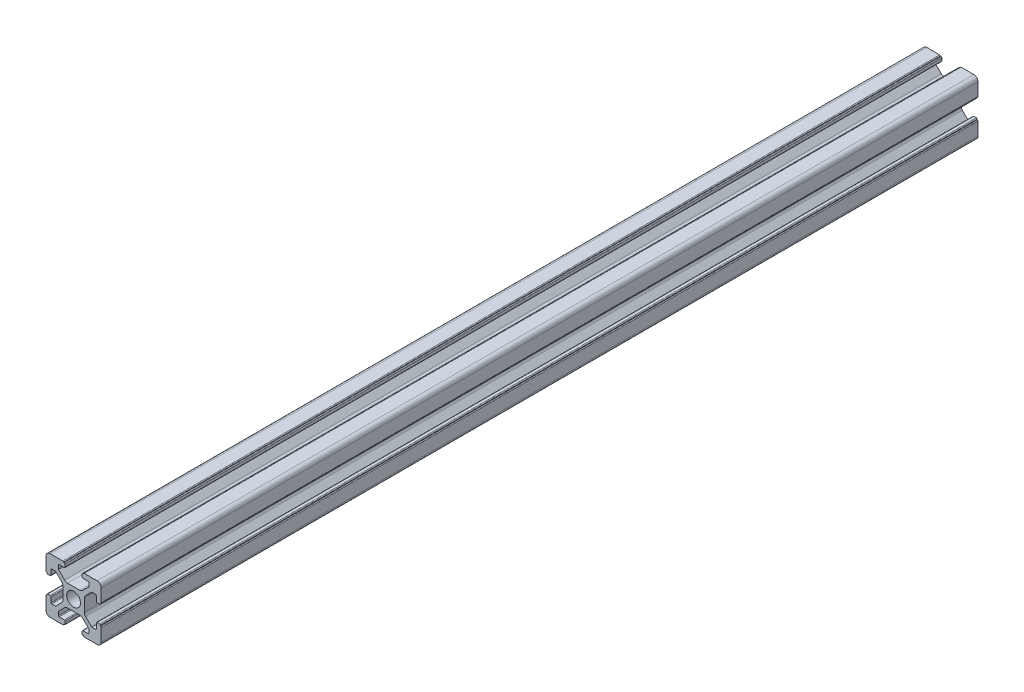
SolidWorks part; units mm, degrees
material "1060 Alloy"
ref_plane "Front Plane" through (0, 0, 0) normal (0, 0, 1) x (1, 0, 0)
ref_plane "Top Plane" through (0, 0, 0) normal (0, 1, 0) x (1, 0, 0)
ref_plane "Right Plane" through (0, 0, 0) normal (1, 0, 0) x (0, 0, -1)
sketch "Sketch1" plane through (0, 0, 0) normal (0, 0, 1) x (1, 0, 0)
  line L0 (3.8995, 3.9005) -> (10.4604, 10.4604) construction
  line L2 (-3.9002, 2.2177) -> (-3.9002, -2.2208)
  line L5 (-3.9005, 3.899) -> (3.9001, -3.8986) construction
  line L6 (-3.9, -3.901) -> (3.8995, 3.9005) construction
  line L7 (-0.0002, 10) -> (-0.0002, -9.9996) construction
  line L8 (-0.0002, -9.9996) -> (-0.0002, 10) construction
  line L9 (5.5006, 6.5619) -> (3.2793, 4.3405)
  line L14 (-10.0002, 9.9996) -> (9.9994, -10) construction
  line L15 (-9.9999, -10.0001) -> (9.9998, 10) construction
  line L16 (6.5613, 5.5012) -> (4.3401, 3.28)
  line L17 (-5.5002, 6.5603) -> (-3.279, 4.3391)
  line L18 (-6.5609, 5.4996) -> (-4.3395, 3.2783)
  line L19 (7.9206, 5.5012) -> (6.5613, 5.5012)
  line L20 (8.2006, 3.3812) -> (8.2006, 5.2212)
  line L21 (9.4206, 3.1012) -> (8.4806, 3.1012)
  line L22 (9.7006, 3.6012) -> (9.7006, 3.3812)
  line L23 (-8.5002, 9.9996) -> (-3.8802, 9.9996)
  line L24 (-3.6002, 9.7196) -> (-3.6002, 9.6996)
  line L25 (-3.6002, 9.6996) -> (-3.3802, 9.6996)
  line L26 (-3.1002, 9.4196) -> (-3.1002, 8.4796)
  line L27 (-3.3802, 8.1996) -> (-5.2202, 8.1996)
  line L28 (-5.5002, 7.9196) -> (-5.5002, 6.5603)
  line L29 (-7.9202, 5.4996) -> (-6.5609, 5.4996)
  line L30 (-8.2002, 3.3796) -> (-8.2002, 5.2196)
  line L31 (-9.4202, 3.0996) -> (-8.4802, 3.0996)
  line L32 (-9.7202, 3.5996) -> (-9.7002, 3.5996)
  line L33 (-9.7002, 3.5996) -> (-9.7002, 3.3796)
  line L34 (-10.0002, 8.4996) -> (-10.0002, 3.8796)
  line L35 (10.0006, 8.5012) -> (10.0006, 3.8812)
  line L36 (8.5006, 10.0012) -> (3.8806, 10.0012)
  line L37 (3.6006, 9.7012) -> (3.3806, 9.7012)
  line L38 (3.1006, 9.4212) -> (3.1006, 8.4812)
  line L39 (3.3806, 8.2012) -> (5.2206, 8.2012)
  line L40 (5.5006, 7.9212) -> (5.5006, 6.5619)
  line L41 (6.5629, -5.4996) -> (4.3415, -3.2783)
  line L42 (5.5022, -6.5603) -> (3.281, -4.3391)
  line L43 (5.5022, -7.9196) -> (5.5022, -6.5603)
  line L44 (3.3822, -8.1996) -> (5.2222, -8.1996)
  line L45 (3.1022, -9.4196) -> (3.1022, -8.4796)
  line L46 (3.6022, -9.6996) -> (3.3822, -9.6996)
  line L47 (8.5022, -9.9996) -> (3.8822, -9.9996)
  line L48 (10.0022, -8.4996) -> (10.0022, -3.8796)
  line L49 (9.7022, -3.5996) -> (9.7022, -3.3796)
  line L50 (9.4222, -3.0996) -> (8.4822, -3.0996)
  line L51 (8.2022, -3.3796) -> (8.2022, -5.2196)
  line L52 (7.9222, -5.4996) -> (6.5629, -5.4996)
  line L53 (-5.4986, -6.5619) -> (-3.2773, -4.3405)
  line L54 (-6.5593, -5.5012) -> (-4.3395, -3.2814)
  line L55 (-7.9186, -5.5012) -> (-6.5593, -5.5012)
  line L56 (-8.1986, -3.3812) -> (-8.1986, -5.2212)
  line L57 (-9.4186, -3.1012) -> (-8.4786, -3.1012)
  line L58 (-9.6986, -3.6012) -> (-9.6986, -3.3812)
  line L59 (-9.9986, -8.5012) -> (-9.9986, -3.8812)
  line L60 (-8.4986, -10.0012) -> (-3.8786, -10.0012)
  line L61 (-3.5986, -9.7012) -> (-3.3786, -9.7012)
  line L62 (-3.0986, -9.4212) -> (-3.0986, -8.4812)
  line L63 (-3.3786, -8.2012) -> (-5.2186, -8.2012)
  line L64 (-5.4986, -7.9212) -> (-5.4986, -6.5619)
  line L65 (-2.233, 3.8998) -> (2.2187, 3.9012)
  line L66 (3.9008, 2.234) -> (3.9022, -2.2177)
  line L67 (2.235, -3.8998) -> (-2.2167, -3.9012)
  line L68 (3.6006, 9.7212) -> (3.6006, 9.6996)
  line L69 (9.7006, 3.6012) -> (9.7206, 3.6012)
  line L70 (-9.6986, -3.6012) -> (-9.7186, -3.6012)
  line L71 (-3.5986, -9.7012) -> (-3.5986, -9.7212)
  line L72 (3.6022, -9.6996) -> (3.6022, -9.7196)
  line L73 (9.7222, -3.5996) -> (9.7022, -3.5996)
  arc A0 (-3.6002, 9.7196) -> (-3.8802, 9.9996) centre (-3.8802, 9.7196) ccw
  arc A1 (-3.3802, 9.6996) -> (-3.1002, 9.4196) centre (-3.3802, 9.4196) cw
  arc A2 (-3.1002, 8.4796) -> (-3.3802, 8.1996) centre (-3.3802, 8.4796) cw
  arc A3 (-10.0002, 8.4996) -> (-8.5002, 9.9996) centre (-8.5002, 8.4996) cw
  arc A4 (-8.2002, 3.3796) -> (-8.4802, 3.0996) centre (-8.4802, 3.3796) cw
  arc A5 (-9.4202, 3.0996) -> (-9.7002, 3.3796) centre (-9.4202, 3.3796) cw
  arc A6 (-9.7202, 3.5996) -> (-10.0002, 3.8796) centre (-9.7202, 3.8796) cw
  arc A7 (-3.279, 4.3391) -> (-2.233, 3.8998) centre (-2.2183, 5.3997) ccw
  arc A8 (-4.3395, 3.2783) -> (-3.9002, 2.2177) centre (-5.4002, 2.2177) cw
  arc A9 (-7.9202, 5.4996) -> (-8.2002, 5.2196) centre (-7.9202, 5.2196) ccw
  arc A10 (-5.2202, 8.1996) -> (-5.5002, 7.9196) centre (-5.2202, 7.9196) ccw
  arc A12 (-4.3395, -3.2814) -> (-3.9002, -2.2208) centre (-5.4002, -2.2208) ccw
  arc A13 (8.2006, 5.2212) -> (7.9206, 5.5012) centre (7.9206, 5.2212) ccw
  arc A14 (8.4806, 3.1012) -> (8.2006, 3.3812) centre (8.4806, 3.3812) cw
  arc A15 (9.7006, 3.3812) -> (9.4206, 3.1012) centre (9.4206, 3.3812) cw
  arc A16 (9.7206, 3.6012) -> (10.0006, 3.8812) centre (9.7206, 3.8812) ccw
  arc A17 (8.5006, 10.0012) -> (10.0006, 8.5012) centre (8.5006, 8.5012) cw
  arc A18 (3.6006, 9.7212) -> (3.8806, 10.0012) centre (3.8806, 9.7212) cw
  arc A19 (3.1006, 9.4212) -> (3.3806, 9.7012) centre (3.3806, 9.4212) cw
  arc A20 (3.3806, 8.2012) -> (3.1006, 8.4812) centre (3.3806, 8.4812) cw
  arc A21 (5.5006, 7.9212) -> (5.2206, 8.2012) centre (5.2206, 7.9212) ccw
  arc A22 (3.2793, 4.3405) -> (2.2187, 3.9012) centre (2.2187, 5.4012) cw
  arc A23 (4.3401, 3.28) -> (3.9008, 2.234) centre (5.4007, 2.2193) ccw
  arc A25 (5.2222, -8.1996) -> (5.5022, -7.9196) centre (5.2222, -7.9196) ccw
  arc A26 (3.1022, -8.4796) -> (3.3822, -8.1996) centre (3.3822, -8.4796) cw
  arc A27 (3.3822, -9.6996) -> (3.1022, -9.4196) centre (3.3822, -9.4196) cw
  arc A28 (3.6022, -9.7196) -> (3.8822, -9.9996) centre (3.8822, -9.7196) ccw
  arc A29 (10.0022, -8.4996) -> (8.5022, -9.9996) centre (8.5022, -8.4996) cw
  arc A30 (9.7222, -3.5996) -> (10.0022, -3.8796) centre (9.7222, -3.8796) cw
  arc A31 (9.4222, -3.0996) -> (9.7022, -3.3796) centre (9.4222, -3.3796) cw
  arc A32 (8.2022, -3.3796) -> (8.4822, -3.0996) centre (8.4822, -3.3796) cw
  arc A33 (7.9222, -5.4996) -> (8.2022, -5.2196) centre (7.9222, -5.2196) ccw
  arc A34 (4.3415, -3.2783) -> (3.9022, -2.2177) centre (5.4022, -2.2177) cw
  arc A35 (3.281, -4.3391) -> (2.235, -3.8998) centre (2.2203, -5.3997) ccw
  circle A36 centre (0.001, -0.001) radius 2.5 construction
  arc A37 (-8.1986, -5.2212) -> (-7.9186, -5.5012) centre (-7.9186, -5.2212) ccw
  arc A38 (-8.4786, -3.1012) -> (-8.1986, -3.3812) centre (-8.4786, -3.3812) cw
  arc A39 (-9.6986, -3.3812) -> (-9.4186, -3.1012) centre (-9.4186, -3.3812) cw
  arc A40 (-9.7186, -3.6012) -> (-9.9986, -3.8812) centre (-9.7186, -3.8812) ccw
  arc A41 (-8.4986, -10.0012) -> (-9.9986, -8.5012) centre (-8.4986, -8.5012) cw
  arc A42 (-3.5986, -9.7212) -> (-3.8786, -10.0012) centre (-3.8786, -9.7212) cw
  arc A43 (-3.0986, -9.4212) -> (-3.3786, -9.7012) centre (-3.3786, -9.4212) cw
  arc A44 (-3.3786, -8.2012) -> (-3.0986, -8.4812) centre (-3.3786, -8.4812) cw
  arc A45 (-5.4986, -7.9212) -> (-5.2186, -8.2012) centre (-5.2186, -7.9212) ccw
  arc A46 (-3.2773, -4.3405) -> (-2.2167, -3.9012) centre (-2.2167, -5.4012) cw
  arc A48 (-4.3381, -3.28) -> (-3.8988, -2.234) centre (-5.3987, -2.2193) ccw [skipped]
  point P0 (0, 0)
  point P9 (-0.0002, 0.0002)
  point P12 (-0.0003, -0.0003)
  point P43 (-3.6002, 9.9996)
  point P46 (-3.1002, 9.6996)
  point P49 (-3.1002, 8.1996)
  point P55 (-8.2002, 3.0996)
  point P58 (-9.7002, 3.0996)
  point P61 (-10.0002, 3.5996)
  point P64 (-2.8395, 3.8996)
  point P67 (-3.9002, 2.839)
  point P70 (-8.2002, 5.4996)
  point P73 (-5.5002, 8.1996)
  point P184 (0.001, 0)
  dimension "D14" = 0.28
  dimension "D15" = 0.28
  dimension "D16" = 0.28
  dimension "D17" = 1.5
  dimension "D18" = 0.28
  dimension "D19" = 1.5
  dimension "D20" = 1.5
  dimension "D21" = 0.28
  dimension "D23" = 5
  dimension "D27" = 1.5
  dimension "D1" = 7.8
  dimension "D2" = 7.8
  dimension "D3" = 3.1
  dimension "D4" = 3.6
  dimension "D5" = 20
  dimension "D6" = 20
  dimension "D7" = 0.75
  dimension "D8" = 1.8
  dimension "D9" = 5.5
  dimension "D10" = 6.4
  dimension "D11" = 6.4
  dimension "D12" = 3.7627
  dimension "D13" = 0.3
  dimension "D24" = 4.62
  dimension "D25" = 3.9005
  dimension "D26" = 7.801
  dimension "D22" = 4
extrude "Boss-Extrude1" add sketch "Sketch1" along normal blind 317.5 contours L53 A46 L67 A35 L42 L43 A25 L44 A26 L45 A27 L46 L72 A28 L47 A29 L48 A30 L73 L49 A31 L50 A32 L51 A33 L52 L41 A34 L66 A23 L16 L19 A13 L20 A14 L21 A15 L22 L69 A16 L35 A17 L36 A18 L68 L37 A19 L38 A20 region at (0.0009, 0, 0)
sketch3d "3DSketch2"
  circle A0 centre (0, 0, 0) radius 2.5
  point P2 (0, 0, 2.5)
extrude "Cut-Extrude1" cut sketch "3DSketch2" along direction (0, 0, 1) on the side of the normal through all contours A0
